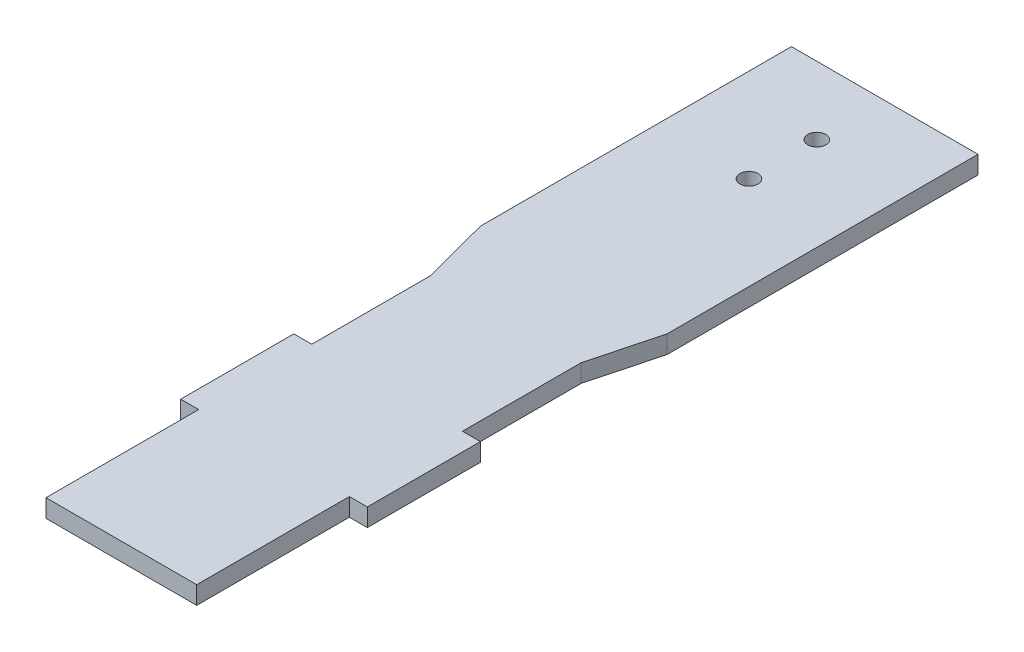
SolidWorks part; units mm, degrees
ref_plane "Front Plane" through (0, 0, 0) normal (0, 0, 1) x (1, 0, 0)
ref_plane "Top Plane" through (0, 0, 0) normal (0, 1, 0) x (1, 0, 0)
ref_plane "Right Plane" through (0, 0, 0) normal (1, 0, 0) x (0, 0, -1)
sketch "Sketch1" plane through (0, 0, 0) normal (0, 1, 0) x (1, 0, 0)
  line L0 (-16.5, 0) -> (16.5, 0)
  line L1 (16.5, 0) -> (16.5, -55)
  line L2 (16.5, -55) -> (13.325, -67)
  line L3 (13.325, -67) -> (13.325, -88)
  line L4 (13.325, -88) -> (16.5, -88)
  line L5 (16.5, -88) -> (16.5, -108)
  line L6 (16.5, -108) -> (13.325, -108)
  line L7 (13.325, -108) -> (13.325, -135)
  line L8 (13.325, -135) -> (-13.325, -135)
  line L9 (0, 0) -> (0, -135) construction
  line L10 (-13.325, -108) -> (-13.325, -135)
  line L11 (-16.5, -108) -> (-13.325, -108)
  line L12 (-16.5, -88) -> (-16.5, -108)
  line L13 (-13.325, -88) -> (-16.5, -88)
  line L14 (-13.325, -67) -> (-13.325, -88)
  line L15 (-16.5, -55) -> (-13.325, -67)
  line L16 (-16.5, 0) -> (-16.5, -55)
  dimension "D1" = 55
  dimension "D2" = 3.175
  dimension "D3" = 20
  dimension "D4" = 33
  dimension "D5" = 27
  dimension "D6" = 16.5
  dimension "D7" = 13.325
  dimension "D8" = 12
extrude "Boss-Extrude1" add sketch "Sketch1" along normal blind 3.175
sketch "Sketch2" plane through (0, 3.175, 0) normal (0, 1, 0) x (1, 0, 0)
  circle A0 centre (0, -24) radius 1.6 construction
  circle A1 centre (0, -12) radius 1.6 construction
  circle A2 centre (0, -24) radius 1.6
  circle A3 centre (0, -12) radius 1.6
extrude "Cut-Extrude1" cut sketch "Sketch2" against normal through all both and the other way through all
